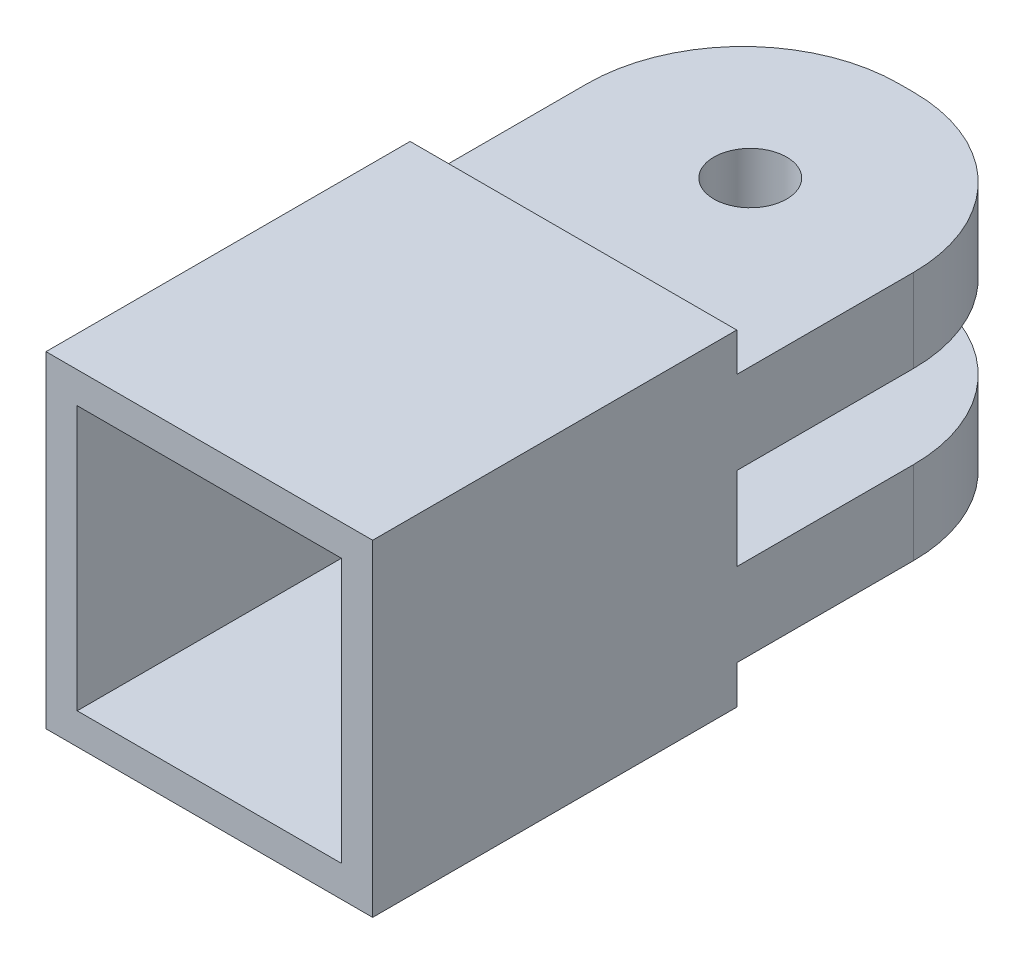
SolidWorks part; units mm, degrees
ref_plane "Front Plane" through (0, 0, 0) normal (0, 0, 1) x (1, 0, 0)
ref_plane "Top Plane" through (0, 0, 0) normal (0, 1, 0) x (1, 0, 0)
ref_plane "Right Plane" through (0, 0, 0) normal (1, 0, 0) x (0, 0, -1)
sketch "Sketch1" plane through (0, 0, 0) normal (0, 0, 1) x (1, 0, 0)
  line L0 (0, 34.2563) -> (0, -38.0151) construction
  line L1 (-50.9145, 0) -> (58.9447, 0) construction
  line L2 (-12.7, 12.7) -> (-12.7, -12.7)
  line L3 (-15.7, 15.7) -> (15.7, 15.7)
  line L4 (-15.7, 15.7) -> (-15.7, -15.7)
  line L5 (-15.7, -15.7) -> (15.7, -15.7)
  line L6 (15.7, 15.7) -> (15.7, -15.7)
  line L7 (-12.7, -12.7) -> (12.7, -12.7)
  line L8 (12.7, 12.7) -> (12.7, -12.7)
  line L9 (-12.7, 12.7) -> (12.7, 12.7)
  dimension "D1" = 15.7
  dimension "D2" = 15.7
  dimension "D3" = 15.7
  dimension "D4" = 15.7
  dimension "D5" = 3
extrude "Boss-Extrude1" add sketch "Sketch1" along normal blind 30
sketch "Sketch2" plane through (0, 0, 0) normal (0, 0, -1) x (-1, 0, 0)
  line L0 (15.7, 15.7) -> (15.7, -15.7)
  line L1 (15.7, -15.7) -> (-15.7, -15.7)
  line L2 (-15.7, -15.7) -> (-15.7, 15.7)
  line L3 (-15.7, 15.7) -> (15.7, 15.7)
extrude "Boss-Extrude2" add sketch "Sketch2" along normal blind 5
sketch "Sketch3" plane through (0, 0, -5) normal (0, 0, -1) x (-1, 0, 0)
  line L6 (-15.7, 12) -> (15.7, 12)
  line L7 (-15.7, 15.7) -> (-15.7, -15.7) construction
  line L8 (15.7, -15.7) -> (15.7, 15.7) construction
  line L9 (15.7, 12) -> (15.7, 4)
  line L10 (15.7, 4) -> (-15.7, 4)
  line L11 (-15.7, 4) -> (-15.7, 12)
  dimension "D1" = 8
  dimension "D2" = 4
extrude "Boss-Extrude3" add sketch "Sketch3" along normal blind 5
sketch "Sketch6" plane through (0, 12, 0) normal (0, 1, 0) x (1, 0, 0)
  line L0 (-15.7, 10) -> (-15.7, 22)
  line L1 (0.7, 37) -> (-0.7, 37)
  line L2 (15.7, 22) -> (15.7, 10)
  line L3 (15.7, 10) -> (-15.7, 10)
  arc A0 (-15.7, 22) -> (-0.7, 37) centre (-0.7, 22) cw
  arc A1 (0.7, 37) -> (15.7, 22) centre (0.7, 22) cw
  circle A2 centre (0, 22) radius 3.5
  point P10 (15.7, 37)
  dimension "D2" = 15
  dimension "D3" = 15
  dimension "D1" = 27
extrude "Boss-Extrude6" add sketch "Sketch6" against normal blind 8
mirror "Mirror1" about plane through (0, 0, 0) normal (0, 1, 0) of "Boss-Extrude6", "Boss-Extrude3"
